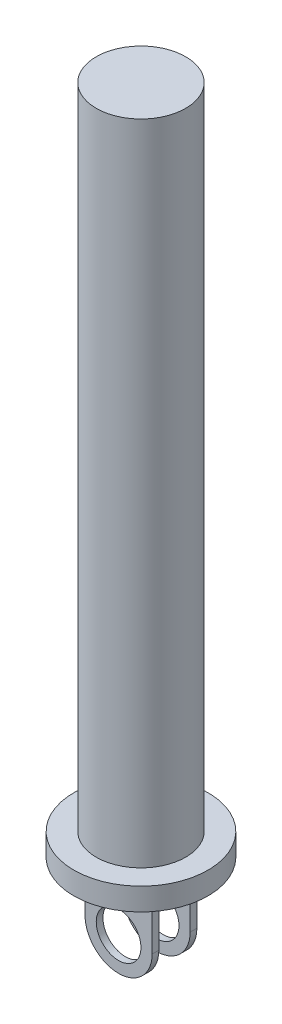
SolidWorks part; units mm, degrees
ref_plane "Front Plane" through (0, 0, 0) normal (0, 0, 1) x (1, 0, 0)
ref_plane "Top Plane" through (0, 0, 0) normal (0, 1, 0) x (1, 0, 0)
ref_plane "Right Plane" through (0, 0, 0) normal (1, 0, 0) x (0, 0, -1)
sketch "Sketch1" plane through (0, 0, 0) normal (0, 1, 0) x (1, 0, 0)
  circle A0 centre (0, 0) radius 15
  dimension "D1" = 30
extrude "Boss-Extrude1" add sketch "Sketch1" along normal blind 5
sketch "Sketch2" plane through (0, 5, 0) normal (0, 1, 0) x (1, 0, 0)
  circle A0 centre (0, 0) radius 10
  dimension "D1" = 20
extrude "Boss-Extrude2" add sketch "Sketch2" along normal blind 145
sketch "Sketch3" plane through (0, 0, 0) normal (0, -1, 0) x (1, 0, 0)
  line L1 (7.5, 5) -> (-7.5, 5)
  line L2 (7.5, 5) -> (7.5, -5)
  line L3 (7.5, -5) -> (-7.5, -5)
  line L4 (-7.5, 5) -> (-7.5, -5)
  line L5 (7.5, 5) -> (-7.5, -5) construction
  line L6 (7.5, -5) -> (-7.5, 5) construction
  point P0 (0, 0)
  dimension "D1" = 10
  dimension "D2" = 15
extrude "Boss-Extrude3" add sketch "Sketch3" along normal blind 20
sketch "Sketch4" plane through (0, 0, 5) normal (0, 0, 1) x (1, 0, 0)
  line L0 (-7.5, -20) -> (-7.5, 0) construction
  line L2 (7.5, -20) -> (-7.5, -20) construction
  circle A0 centre (0, -12.5) radius 5
  point P4 (0, 0)
  dimension "D1" = 10
  dimension "D2" = 7.5
  dimension "D3" = 7.5
extrude "Cut-Extrude1" cut sketch "Sketch4" against normal through all both and the other way through all
sketch "Sketch5" plane through (0, -20, 0) normal (0, -1, 0) x (1, 0, 0)
  line L0 (-7.5, 5) -> (-7.5, -5) construction
  line L1 (-7.5, 3.5) -> (7.5, 3.5)
  line L2 (-7.5, 3.5) -> (-7.5, -3.5)
  line L3 (-7.5, -3.5) -> (7.5, -3.5)
  line L4 (7.5, 3.5) -> (7.5, -3.5)
  line L5 (7.5, -5) -> (7.5, 5) construction
  line L6 (-7.5, -5) -> (7.5, -5) construction
  point P8 (-7.5, 0)
  dimension "D1" = 7
  dimension "D2" = 5
extrude "Cut-Extrude2" cut sketch "Sketch5" against normal blind 15 and the other way through all
fillet "Fillet1" radius 7.5 4 edges at (7.5, -20, 4.25) (7.5, -20, -4.25) (-7.5, -20, 4.25) (-7.5, -20, -4.25)
